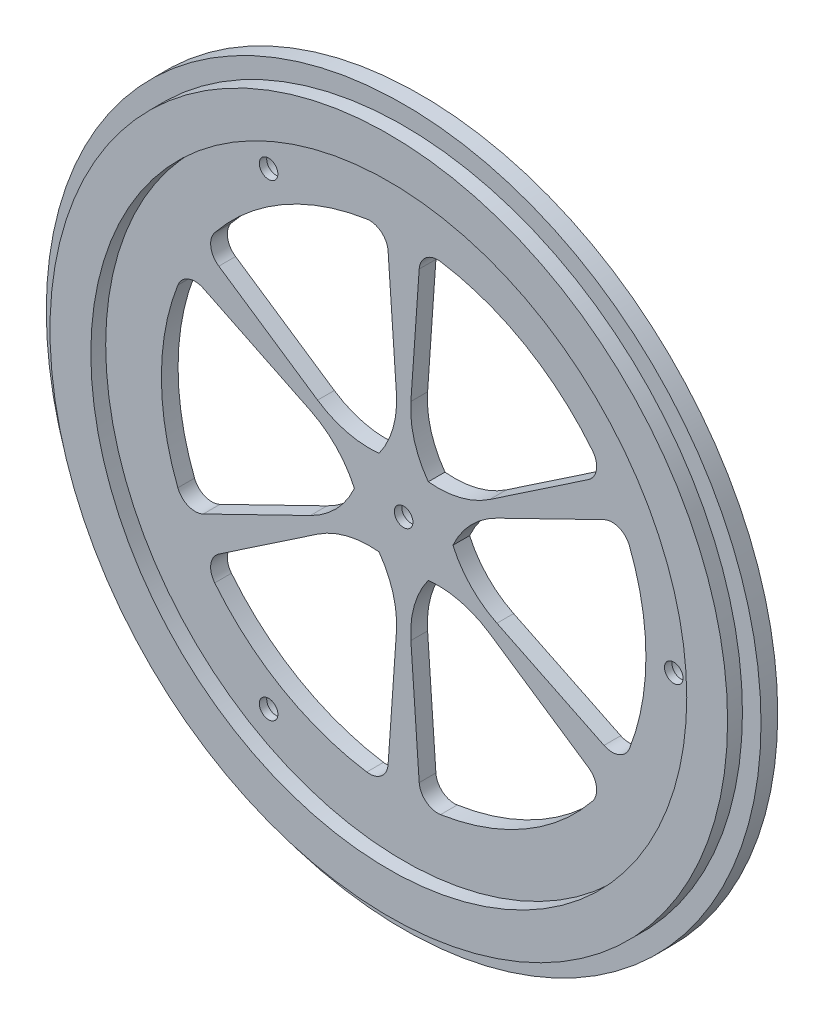
SolidWorks part; units mm, degrees
ref_plane "前视基准面" through (0, 0, 0) normal (0, 0, 1) x (1, 0, 0)
ref_plane "上视基准面" through (0, 0, 0) normal (0, 1, 0) x (1, 0, 0)
ref_plane "右视基准面" through (0, 0, 0) normal (1, 0, 0) x (0, 0, -1)
other "Configuration Table"
sketch "草图1" plane through (0, 0, 0) normal (0, 0, 1) x (1, 0, 0)
  circle A0 centre (0, 0) radius 38.5
  dimension "D1" = 77
extrude "凸台-拉伸1" add sketch "草图1" along normal blind 2
sketch "草图2" plane through (0, 0, 2) normal (0, 0, 1) x (1, 0, 0)
  circle A0 centre (0, 0) radius 36.5
  circle A1 centre (0, 0) radius 32.1
  dimension "D1" = 73
  dimension "D2" = 64.2
extrude "切除-拉伸1" cut sketch "草图2" against normal blind 0.2 flip side to cut
extrude "凸台-拉伸2" add sketch "草图2<2>" along normal blind 1.4
sketch "草图2<2>" plane through (0, 0, 2) normal (0, 0, 1) x (1, 0, 0) same geometry as "草图2"
sketch "草图3" plane through (0, 0, 1.8) normal (0, 0, 1) x (1, 0, 0)
  line L0 (0, 0) -> (0, 26.1) construction
  line L1 (-1.8206, 26.0364) -> (0, 0)
  line L2 (0, 0) -> (1.8206, 26.0364)
  line L3 (-1.8206, 26.0364) -> (1.8206, 26.0364) construction
  circle A0 centre (0, 0) radius 26.1
  circle A1 centre (0, 0) radius 5
  point P6 (0, 26.0364)
  dimension "D1" = 52.2
  dimension "D2" = 10
  dimension "D3" = 8
extrude "切除-拉伸2" cut sketch "草图3" against normal through all contours A0
extrude "凸台-拉伸3" add sketch "草图3<3>" against normal through all separate body contours A1
sketch "草图3<3>" plane through (0, 0, 1.8) normal (0, 0, 1) x (1, 0, 0) same geometry as "草图3"
extrude "凸台-拉伸4" add sketch "草图3<4>" against normal through all contours A1 L2 A0 L1 region at (0, 17.9213, 1.8)
sketch "草图3<4>" plane through (0, 0, 1.8) normal (0, 0, 1) x (1, 0, 0) same geometry as "草图3"
fillet "圆角1" radius 2 2 edges at (-1.8206, 26.0364, 0.9) (1.8206, 26.0364, 0.9)
pattern_circular "阵列(圆周)1" count 6 over 360 about axis through (0, 0, 2) along (0, 0, -1) of "圆角1", "凸台-拉伸4"
fillet "圆角2" radius 10 12 edges at (4.494, -2.1919, 0.9) (4.494, 2.1919, 0.9) (0.3488, -4.9878, 0.9) (4.1452, -2.796, 0.9) (-4.1452, -2.796, 0.9) (-0.3488, -4.9878, 0.9) (-4.494, -2.1919, 0.9) (-4.494, 2.1919, 0.9) (-4.1452, 2.796, 0.9) (-0.3488, 4.9878, 0.9) (4.1452, 2.796, 0.9) (0.3488, 4.9878, 0.9)
sketch "草图4" plane through (0, 0, 1.8) normal (0, 0, 1) x (1, 0, 0)
  line L2 (0, 0) -> (-16.05, 27.7994) construction
  line L3 (0, 0) -> (32.1, 0) construction
  line L4 (0, 0) -> (-16.05, -27.7994) construction
  circle A1 centre (0, 0) radius 32.1 construction
  circle A2 centre (0, 0) radius 26.1 construction
  arc A3 (-3.9751, 25.7955) -> (-20.352, 16.3403) centre (0, 0) ccw construction
  circle A5 centre (11.3209, 26.8076) radius 3 construction
  circle A6 centre (0, 0) radius 29.1 construction
  circle A7 centre (-14.55, 25.2013) radius 1.5
  circle A8 centre (29.1, 0) radius 1.5
  circle A9 centre (-14.55, -25.2013) radius 1.5
  circle A10 centre (0, 0) radius 1.5
  circle A11 centre (-14.55, 25.2013) radius 1
  circle A12 centre (0, 0) radius 1
  circle A13 centre (29.1, 0) radius 1
  circle A14 centre (-14.55, -25.2013) radius 1
  dimension "D3" = 64.2
  dimension "D4" = 3
  dimension "D5" = 2
  dimension "D1" = 120
  dimension "D2" = 120
extrude "切除-拉伸3" cut sketch "草图4" against normal through all contours A12 | A13 | A14 | A11
extrude "切除-拉伸4" cut sketch "草图4<3>" along normal blind 1 from surface contours A7 | A10 | A9 | A8 starting at face at (-13.55, 25.2013, 0)
sketch "草图4<3>" plane through (0, 0, 1.8) normal (0, 0, 1) x (1, 0, 0) same geometry as "草图4"
